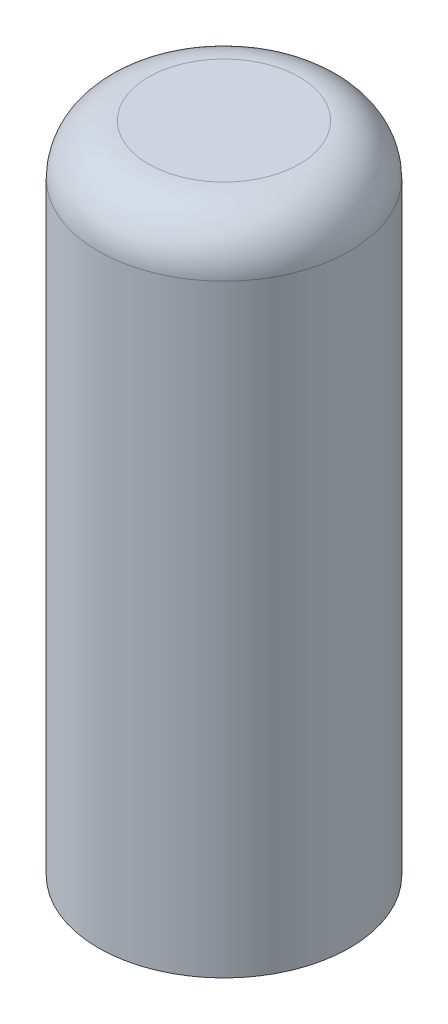
SolidWorks part; units mm, degrees
ref_plane "Front Plane" through (0, 0, 0) normal (0, 0, 1) x (1, 0, 0)
ref_plane "Top Plane" through (0, 0, 0) normal (0, 1, 0) x (1, 0, 0)
ref_plane "Right Plane" through (0, 0, 0) normal (1, 0, 0) x (0, 0, -1)
sketch "Sketch2" plane through (0, 0, 0) normal (0, 1, 0) x (1, 0, 0)
  line L1 (-0.975, 0.6) -> (0.975, 0.6)
  line L2 (-0.975, 0.6) -> (-0.975, -0.6)
  line L3 (-0.975, -0.6) -> (0.975, -0.6)
  line L4 (0.975, 0.6) -> (0.975, -0.6)
  line L5 (-0.975, 0.6) -> (0.975, -0.6) construction
  line L6 (-0.975, -0.6) -> (0.975, 0.6) construction
  circle A0 centre (0, 0) radius 2.5
  dimension "D1" = 5
  dimension "D2" = 1.2
  dimension "D3" = 1.95
extrude "Boss-Extrude1" add sketch "Sketch2" along normal mid plane 13
fillet "Fillet1" radius 1 1 edges at (0, 6.5, 2.5)
sketch "Sketch3" plane through (0, 6.5, 0) normal (0, 1, 0) x (1, 0, 0)
  line L0 (0.975, -0.6) -> (0.975, 0.6) construction
  line L1 (-0.975, -0.6) -> (0.975, -0.6) construction
  line L2 (-0.975, 0.6) -> (-0.975, -0.6) construction
  line L3 (0.975, 0.6) -> (-0.975, 0.6) construction
  line L4 (0.975, -0.6) -> (0.975, 0.6)
  line L5 (-0.975, -0.6) -> (0.975, -0.6)
  line L6 (-0.975, 0.6) -> (-0.975, -0.6)
  line L7 (0.975, 0.6) -> (-0.975, 0.6)
extrude "Boss-Extrude5" add sketch "Sketch3" against normal blind 1
